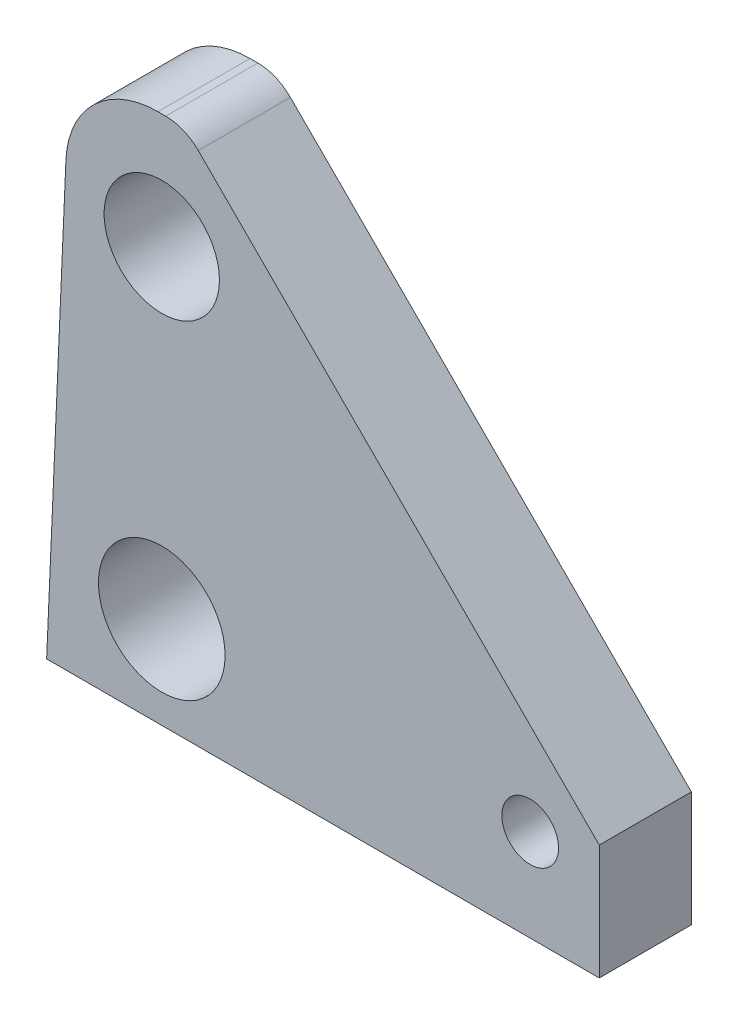
SolidWorks part; units mm, degrees
material "Delrin (Acetal)"
ref_plane "Front Plane" through (0, 0, 0) normal (0, 0, 1) x (1, 0, 0)
ref_plane "Top Plane" through (0, 0, 0) normal (0, 1, 0) x (1, 0, 0)
ref_plane "Right Plane" through (0, 0, 0) normal (1, 0, 0) x (0, 0, -1)
sketch "Sketch1" plane through (0, 0, 0) normal (1, 0, 0) x (0, 0, -1)
  line L0 (0, 18.2562) -> (0, -18.2562)
  dimension "D1" = 36.5125
sheet metal parameters "Sheet-Metal1" thickness 6.35 parameters "D1"=1.5875
base flange "Base-Flange1" sketch "Sketch1" end condition mid plane depth 38.1 reverse direction no thickness 6.35 reverse thickness direction no bend radius 1.5875
sketch "Sketch3" plane through (0, 0, 6.35) normal (0, 0, 1) x (1, 0, 0)
  line L0 (-19.05, 18.2562) -> (-19.05, -18.2562) construction
  line L1 (-19.05, 18.2562) -> (-19.05, -18.2562)
  line L2 (19.05, 18.2562) -> (-19.05, 18.2562) construction
  line L3 (-17.4558, 18.2562) -> (-19.05, 18.2562)
  line L4 (-19.05, -18.2562) -> (-17.4558, 18.2562)
  line L5 (19.05, 18.2562) -> (19.05, -18.2562) construction
  line L6 (19.05, 18.2562) -> (19.05, -10.3187)
  line L7 (19.05, 18.2562) -> (-9.525, 18.2563)
  line L8 (-9.525, 18.2563) -> (19.05, -10.3187)
  line L9 (19.05, -18.2562) -> (-19.05, -18.2562) construction
  dimension "D1" = 2.5
  dimension "D2" = 7.9375
  dimension "D3" = 45
extrude "Cut-Extrude1" cut sketch "Sketch3" against normal up to next normal cut yes
sketch "Sketch4" plane through (0, 0, 6.35) normal (0, 0, 1) x (1, 0, 0)
  line L0 (-9.525, 18.2562) -> (-17.4558, 18.2562) construction
  circle A0 centre (-11.1125, -11.9062) radius 4.3656
  circle A1 centre (14.2875, -11.9062) radius 1.9558
  circle A2 centre (-11.1125, 10.3187) radius 3.9751
  dimension "D5" = 8.7312
  dimension "D6" = 3.9116
  dimension "D7" = 7.9502
  dimension "D1" = 25.4
  dimension "D2" = 7.9375
  dimension "D3" = 22.225
  dimension "D4" = 7.9375
extrude "Cut-Extrude2" cut sketch "Sketch4" against normal up to next normal cut yes
fillet "Fillet1" radius 6.35 1 edges at (-17.4558, 18.2562, 3.175)
fillet "Fillet2" radius 3.175 1 edges at (-9.525, 18.2562, 3.175)
flat pattern "Flat-Pattern1" [suppressed]
sketch "Bend-Lines1" plane through (0, 0, 0) normal (0, 1, 0) x (-1, 0, 0)
sketch3d "Bounding-Box1" [suppressed]
  line L0 (0, -36.5125, 0) -> (38.1, -36.5125, 0) construction
  line L1 (0, 0, 0) -> (38.1, 0, 0) construction
  line L2 (0, -36.5125, 0) -> (0, 0, 0) construction
  line L3 (38.1, -36.5125, 0) -> (38.1, 0, 0) construction
